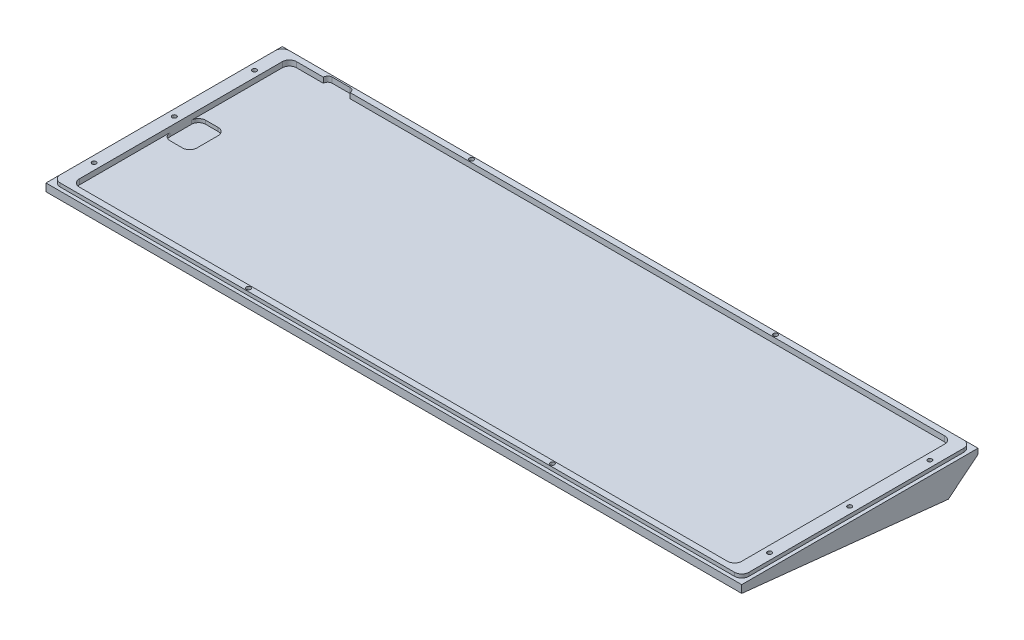
SolidWorks part; units mm, degrees
ref_plane "Front Plane" through (0, 0, 0) normal (0, 0, 1) x (1, 0, 0)
ref_plane "Top Plane" through (0, 0, 0) normal (0, 1, 0) x (1, 0, 0)
ref_plane "Right Plane" through (0, 0, 0) normal (1, 0, 0) x (0, 0, -1)
sketch "Sketch1" plane through (0, 0, 0) normal (0, 1, 0) x (1, 0, 0)
  line L1 (0, 0) -> (390.7, 0)
  line L2 (0, 0) -> (0, 132.7)
  line L3 (0, 132.7) -> (390.7, 132.7)
  line L4 (390.7, 0) -> (390.7, 132.7)
  dimension "D1" = 390.7
  dimension "D2" = 132.7
extrude "MainBody" add sketch "Sketch1" along normal blind 18.5
sketch "Sketch2" plane through (0, 18.5, 0) normal (0, 1, 0) x (1, 0, 0)
  line L0 (390.7, 132.7) -> (0, 132.7) construction
  line L1 (2, 130.7) -> (388.7, 130.7)
  line L2 (2, 130.7) -> (2, 2)
  line L3 (2, 2) -> (388.7, 2)
  line L4 (388.7, 130.7) -> (388.7, 2)
  line L5 (0, 132.7) -> (0, 0) construction
  line L7 (0, 132.7) -> (390.7, 132.7)
  line L8 (0, 132.7) -> (0, 0)
  line L9 (0, 0) -> (390.7, 0)
  line L10 (390.7, 132.7) -> (390.7, 0)
  point P4 (195.35, 130.7)
  point P7 (195.35, 132.7)
  point P8 (2, 66.35)
  point P11 (0, 66.35)
  line M5 (0, 132.7) -> (0, 0)
  line M6 (0, 0) -> (390.7, 0)
  line M7 (390.7, 0) -> (390.7, 132.7)
  line M8 (390.7, 132.7) -> (0, 132.7)
  dimension "D1" = 2
  dimension "D2" = 2
extrude "AligmentLip" cut sketch "Sketch2" against normal blind 2 contours L1 L4 L3 L2 M8 M5 M6 M7 region at (195.35, 18.5, -132.2874)
sketch "Sketch3" plane through (0, 0, 0) normal (-1, 0, 0) x (0, 0, 1)
  line L0 (-132.7, 13.5) -> (-116.0289, 0)
  line L1 (-132.7, 16.5) -> (-132.7, 0) construction
  line L2 (-132.7, 0) -> (0, 0) construction
  line L3 (-116.0289, 0) -> (0, 12.1951)
  line L4 (0, 16.5) -> (0, 0) construction
  line L5 (-132.7, 16.5) -> (0, 16.5) construction
  line L7 (-132.7, 16.5) -> (0, 16.5)
  line L8 (-132.7, 16.5) -> (-132.7, 0)
  line L9 (-132.7, 0) -> (0, 0)
  line L10 (0, 16.5) -> (0, 0)
  line M4 (-132.7, 16.5) -> (-132.7, 0)
  line M5 (-132.7, 0) -> (0, 0)
  line M6 (0, 0) -> (0, 16.5)
  dimension "D1" = 6
  dimension "D2" = 135
  dimension "D3" = 3
extrude "TypingAngle" cut sketch "Sketch3" against normal through all contours L0 M4 M5 | L3 M5 M6 region at (0, 4.5, -127.143) region at (0, 4.065, -38.6763)
sketch "Sketch4" plane through (0, 18.5, 0) normal (0, 1, 0) x (1, 0, 0)
  line L0 (2, 130.7) -> (388.7, 130.7) construction
  line L1 (9.35, 127.35) -> (381.35, 127.35)
  line L2 (9.35, 127.35) -> (9.35, 5.35)
  line L3 (9.35, 5.35) -> (381.35, 5.35)
  line L4 (381.35, 127.35) -> (381.35, 5.35)
  line L5 (2, 130.7) -> (2, 2) construction
  point P4 (195.35, 127.35)
  point P7 (195.35, 130.7)
  point P8 (9.35, 66.35)
  point P11 (2, 66.35)
  dimension "D1" = 372
  dimension "D2" = 122
extrude "PCBCutout" cut sketch "Sketch4" against normal blind 3
sketch3d "3DSketch2"
  line L1 (390.7, 0, -116.0289) -> (390.7, 12.1951, 0) construction
  line L3 (390.7, 7.5626, -100.812) -> (390.7, 1.3066, -103.5974)
  line L6 (390.7, 8.5366, -34.8083) -> (390.7, 10.4246, -37.1397)
  line L9 (390.7, 12.6516, -43.2584) -> (390.7, 13.4937, -91.502)
  arc A0 (390.7, 10.4246, -37.1397) -> (390.7, 12.6516, -43.2584) centre (390.7, 2.6531, -43.4329) cw
  arc A1 (390.7, 7.5626, -100.812) -> (390.7, 13.4937, -91.502) centre (390.7, 3.4952, -91.6766) cw
  point P10 (380.7, 2.6531, -43.4329)
  point P12 (400.7, 3.4952, -91.6766)
  dimension "D1" = 10
  dimension "D2" = 10
  dimension "D3" = 3
  dimension "D4" = 7
  dimension "D5" = 135
  dimension "D6" = 35
  dimension "D8" = 12.5
  dimension "D7" = 60
sketch "Sketch5" plane through (0, 12.0619, -1.2678) normal (0, -0.9945, 0.1045) x (1, 0, 0)
  line L0 (390.7, -33.7253) -> (388.5787, -35.8466)
  line L1 (385.7243, -41.699) -> (379.844, -89.5903)
  line L2 (384.7694, -99.4693) -> (390.7, -102.8933)
  line L3 (390.7, -115.3933) -> (390.7, 1.2747) construction
  arc A0 (388.5787, -35.8466) -> (385.7243, -41.699) centre (395.6497, -42.9177) ccw
  arc A1 (379.844, -89.5903) -> (384.7694, -99.4693) centre (389.7694, -90.809) ccw
  dimension "D3" = 10
  dimension "D4" = 10
  dimension "D1" = 7
  dimension "D2" = 3
  dimension "D5" = 60
  dimension "D6" = 45
sketch3d "3DSketch3"
  line L0 (390.7, 13.4937, -91.502) -> (379.844, 2.6971, -90.3673)
  line L1 (390.7, 12.6516, -43.2584) -> (385.7243, 7.7032, -42.7383)
loft "RightCutout" [suppressed] cut section "Sketch5" section "3DSketch2"
sketch3d "Centerline" [suppressed]
  line L0 (195.35, 15.5, -127.35) -> (195.35, 18.5, -5.35) construction
  line L1 (381.35, 15.5, -127.35) -> (9.35, 15.5, -127.35) construction
  line L2 (9.35, 18.5, -5.35) -> (381.35, 18.5, -5.35) construction
ref_plane "CenterMirrorPlane" [suppressed] through (195.35, 0, 0) normal (-1, 0, 0) x (0, 0, 1)
sketch "Sketch6" plane through (0, 18.5, 0) normal (0, 1, 0) x (1, 0, 0)
  line L0 (390.7, 132.7) -> (0, 132.7) construction
  line L1 (195.35, 132.7) -> (0, 132.7)
  line L2 (195.35, 132.7) -> (195.35, 0)
  line L3 (195.35, 0) -> (0, 0)
  line L4 (0, 132.7) -> (0, 0)
extrude "HalfBodyRemove" [suppressed] cut sketch "Sketch6" against normal through all
mirror "LeftCutout" [suppressed] about plane through (195.35, 0, 0) normal (-1, 0, 0) of bodies 113
sketch "Sketch8" plane through (0, 18.5, 0) normal (0, 1, 0) x (1, 0, 0)
  line L0 (195.35, 132.7) -> (195.35, 0) construction
  line L1 (390.7, 132.7) -> (0, 132.7) construction
  line L2 (0, 0) -> (390.7, 0) construction
  line L3 (0, 66.35) -> (195.35, 66.35) construction
  line L4 (0, 132.7) -> (0, 0) construction
  line L5 (2, 130.7) -> (388.7, 130.7) construction
  line L6 (2, 2) -> (388.7, 2) construction
  line L7 (2, 130.7) -> (2, 2) construction
  point P11 (110, 129)
  point P12 (5.7, 111.35)
  point P13 (5.7, 66.35)
  point P14 (5.7, 21.35)
  point P16 (110, 3.7)
  point P27 (280.7, 3.7)
  point P28 (385, 21.35)
  point P29 (385, 66.35)
  point P30 (385, 111.35)
  point P31 (280.7, 129)
  dimension "D1" = 1.7
  dimension "D2" = 1.7
  dimension "D3" = 110
  dimension "D4" = 45
  dimension "D5" = 45
  dimension "D6" = 3.7
hole_wizard "M2 Clearance Hole2" positions "3DSketch7" profile "Sketch10" hole size "M2" standard "ANSI Metric" end condition through all
sketch3d "3DSketch7"
  point P0 (110, 18.5, -129)
  point P3 (5.7, 18.5, -111.35)
  point P6 (5.7, 18.5, -66.35)
  point P9 (5.7, 18.5, -21.35)
  point P12 (110, 18.5, -3.7)
  point P15 (280.7, 18.5, -129)
  point P18 (280.7, 18.5, -3.7)
  point P21 (385, 18.5, -21.35)
  point P24 (385, 18.5, -66.35)
  point P27 (385, 18.5, -111.35)
sketch "Sketch10" plane through (110, 18.5, -129) normal (1, 0, 0) x (0, 0, 1)
  line L0 (0, 0) -> (0, 18.5)
  line L1 (0, 18.5) -> (1.2, 18.5)
  line L2 (1.2, 18.5) -> (1.2, 0)
  line L5 (1.2, 0) -> (0, 0)
  line L11 (0, -6.35) -> (0, 107.95) construction
  dimension "Thru Hole Dia." = 2.4
  dimension "Thru Hole Depth" = 18.5
sketch "Sketch11" plane through (0, 15.5, 0) normal (0, 1, 0) x (1, 0, 0)
  line L0 (195.35, 132.7) -> (195.35, 0) construction
  line L1 (0, 0) -> (390.7, 0) construction
  circle A0 centre (110, 129) radius 2.5
  circle A1 centre (5.7, 111.35) radius 2.5
  circle A2 centre (5.7, 66.35) radius 2.5
  circle A3 centre (5.7, 21.35) radius 2.5
  circle A4 centre (110, 3.7) radius 2.5
  circle A5 centre (280.7, 3.7) radius 2.5
  circle A6 centre (385, 21.35) radius 2.5
  circle A7 centre (385, 66.35) radius 2.5
  circle A8 centre (385, 111.35) radius 2.5
  circle A9 centre (280.7, 129) radius 2.5
  dimension "D1" = 5
extrude "Cut-Extrude2" cut sketch "Sketch11" against normal through all from offset 1 offset against normal yes
sketch "Sketch12" plane through (0, 18.5, 0) normal (0, 1, 0) x (1, 0, 0)
  line L0 (381.35, 127.35) -> (9.35, 127.35) construction
  line L1 (28.4, 127.35) -> (43.4, 127.35)
  line L2 (28.4, 127.35) -> (28.4, 129.85)
  line L3 (28.4, 129.85) -> (43.4, 129.85)
  line L4 (43.4, 127.35) -> (43.4, 129.85)
  line L5 (0, 132.7) -> (0, 0) construction
  point P6 (35.9, 129.85)
  dimension "D1" = 15
  dimension "D2" = 2.5
  dimension "D3" = 35.9
extrude "Cut-Extrude3" cut sketch "Sketch12" against normal up to surface (3 mm away) up to face at (195.35, 15.5, -66.35)
fillet "Fillet1" radius 2.5 2 edges at (43.4, 17, -129.85) (28.4, 17, -129.85)
sketch "Sketch13" plane through (0, 15.5, 0) normal (0, 1, 0) x (1, 0, 0)
  line L0 (9.35, 127.35) -> (9.35, 5.35) construction
  line L1 (9.35, 76.35) -> (24.35, 76.35)
  line L2 (9.35, 76.35) -> (9.35, 56.35)
  line L3 (9.35, 56.35) -> (24.35, 56.35)
  line L4 (24.35, 76.35) -> (24.35, 56.35)
  line L5 (2, 130.7) -> (2, 2) construction
  point P6 (9.35, 66.35)
  point P9 (2, 66.35)
  dimension "D1" = 15
  dimension "D2" = 20
extrude "Cut-Extrude4" cut sketch "Sketch13" against normal blind 2
fillet "Fillet2" radius 4 12 edges at (381.35, 17, -127.35) (388.7, 17.5, -130.7) (388.7, 17.5, -2) (381.35, 17, -5.35) (9.35, 17, -5.35) (2, 17.5, -2) (9.35, 17, -127.35) (2, 17.5, -130.7) (9.35, 14.5, -56.35) (24.35, 14.5, -56.35) (9.35, 14.5, -76.35) (24.35, 14.5, -76.35)
